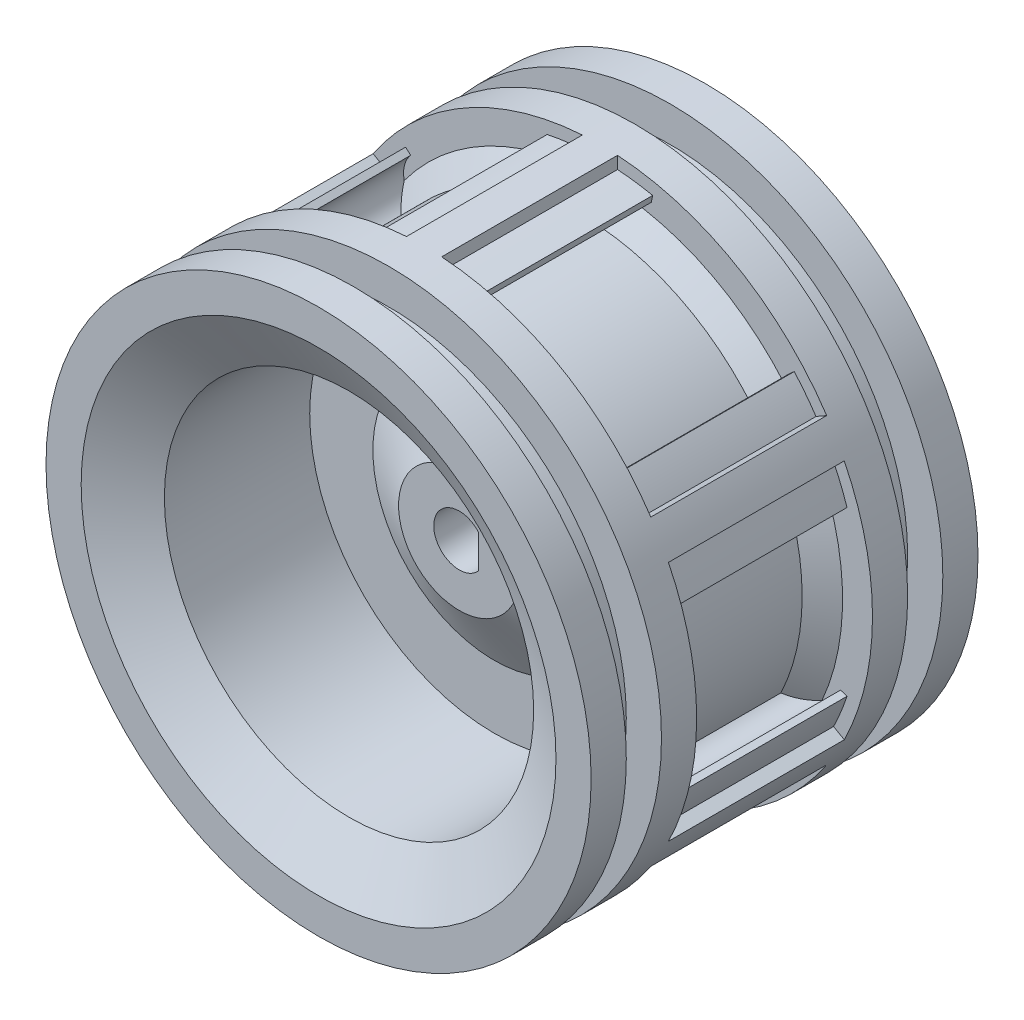
SolidWorks part; units mm, degrees
material "ABS"
ref_plane "Спереди" through (0, 0, 0) normal (0, 0, 1) x (1, 0, 0)
ref_plane "Сверху" through (0, 0, 0) normal (0, 1, 0) x (1, 0, 0)
ref_plane "Справа" through (0, 0, 0) normal (1, 0, 0) x (0, 0, -1)
sketch "Эскиз2" plane through (0, 0, 0) normal (1, 0, 0) x (0, 0, -1)
  line L0 (0, 19.2781) -> (0, -11.4066) construction
  line L1 (-12.1445, 0) -> (10.5473, 0) construction
  line L2 (4, 12.5) -> (-4, 12.5)
  line L3 (-4, 12.5) -> (-5, 13.799)
  line L4 (-5, 13.799) -> (-5, 15.5)
  line L5 (-5, 15.5) -> (-7, 15.5)
  line L6 (-7, 15.5) -> (-7, 13.5)
  line L7 (-7, 13.5) -> (-9, 13.5)
  line L8 (-9, 13.5) -> (-9, 15.5)
  line L9 (-9, 15.5) -> (-11, 15.5)
  line L10 (-11, 15.5) -> (-11, 13.5)
  line L11 (-11, 13.5) -> (-9.2679, 10.5)
  line L12 (-9.2679, 10.5) -> (-1.0033, 10.5)
  line L15 (10.5, 10.5) -> (10.5, 4.45)
  line L17 (11, 15.5) -> (11, 13.5)
  line L18 (9, 15.5) -> (11, 15.5)
  line L19 (9, 13.5) -> (9, 15.5)
  line L20 (7, 13.5) -> (9, 13.5)
  line L21 (7, 15.5) -> (7, 13.5)
  line L22 (5, 15.5) -> (7, 15.5)
  line L23 (5, 13.799) -> (5, 15.5)
  line L24 (4, 12.5) -> (5, 13.799)
  line L25 (10.5, 1.45) -> (-3, 1.45)
  line L26 (-3, 1.45) -> (-3, 3.45)
  line L27 (-3, 3.45) -> (-1.0033, 6.9084)
  line L28 (-1.0033, 6.9084) -> (-1.0033, 10.5)
  line L31 (11, 13.5) -> (10.5, 10.5)
  line L32 (10.5, 1.45) -> (13.5, 1.45)
  line L33 (10.5, 6.2924) -> (10.5, -2.5086) construction
  arc A0 (13.5, 1.45) -> (11.5, 3.45) centre (11.5, 1.45) ccw
  arc A1 (11.5, 3.45) -> (10.5, 4.45) centre (11.5, 4.45) cw
  dimension "D1" = 2
  dimension "D17" = 3
  dimension "D18" = 1
  dimension "D19" = 2
  dimension "D2" = 31
  dimension "D3" = 2
  dimension "D4" = 2
  dimension "D5" = 2
  dimension "D6" = 3
  dimension "D7" = 8
  dimension "D8" = 10
  dimension "D9" = 2
  dimension "D10" = 60
  dimension "D11" = 3
  dimension "D12" = 2.9
  dimension "D13" = 0.5
  dimension "D14" = 30
  dimension "D15" = 2
  dimension "D16" = 14
revolve "Повернуть1" add sketch "Эскиз2" angle 360 about L1 region at (0, 8.2036, -3.011)
sketch "Эскиз3" plane through (0, 0, 1.0033) normal (0, 0, 1) x (1, 0, 0)
  line L0 (-3.8268, 9.2388) -> (0, 0) construction
  line L1 (0, 0) -> (3.8268, 9.2388) construction
  line L2 (0, 16.141) -> (0, -17.0298) construction
  line L3 (-3.8268, 9.2388) -> (-2.8351, 6.8444) construction
  arc A1 (-3.8268, 9.2388) -> (3.8268, 9.2388) centre (0, 0) cw
  arc A2 (-2.8351, 6.8444) -> (2.8351, 6.8444) centre (0, 0) cw
  arc A3 (-2.8351, 6.8444) -> (-3.8268, 9.2388) centre (-3.3309, 8.0416) cw
  circle A4 centre (0, 0) radius 10.5 construction
  arc A5 (3.8268, 9.2388) -> (2.8351, 6.8444) centre (3.3309, 8.0416) cw
  circle A6 centre (0, 0) radius 6.9084 construction
  arc A7 (-3.3309, 8.0416) -> (3.3309, 8.0416) centre (0, 0) cw construction
  arc A8 (9.2388, -3.8268) -> (6.8444, -2.8351) centre (8.0416, -3.3309) cw
  arc A9 (6.8444, 2.8351) -> (6.8444, -2.8351) centre (0, 0) cw
  arc A10 (6.8444, 2.8351) -> (9.2388, 3.8268) centre (8.0416, 3.3309) cw
  arc A11 (9.2388, 3.8268) -> (9.2388, -3.8268) centre (0, 0) cw
  arc A12 (-3.8268, -9.2388) -> (-2.8351, -6.8444) centre (-3.3309, -8.0416) cw
  arc A13 (2.8351, -6.8444) -> (-2.8351, -6.8444) centre (0, 0) cw
  arc A14 (2.8351, -6.8444) -> (3.8268, -9.2388) centre (3.3309, -8.0416) cw
  arc A15 (3.8268, -9.2388) -> (-3.8268, -9.2388) centre (0, 0) cw
  arc A16 (-9.2388, 3.8268) -> (-6.8444, 2.8351) centre (-8.0416, 3.3309) cw
  arc A17 (-6.8444, -2.8351) -> (-6.8444, 2.8351) centre (0, 0) cw
  arc A18 (-6.8444, -2.8351) -> (-9.2388, -3.8268) centre (-8.0416, -3.3309) cw
  arc A19 (-9.2388, -3.8268) -> (-9.2388, 3.8268) centre (0, 0) cw
  point P51 (0, 0)
  dimension "D1" = 45
  dimension "D2" = 0.5
  dimension "D3" = 0.5
  dimension "D4" = 4
extrude "Вырез-Вытянуть1" [suppressed] cut sketch "Эскиз3" against normal through all contours A5 A1 A3 A2 | A11 A10 A9 A8 | A15 A14 A13 A12 | A19 A18 A17 A16
sketch "Эскиз4" plane through (0, 0, 0) normal (0, 0, 1) x (1, 0, 0)
  line L0 (-1, 15.4677) -> (-1, 14.7662)
  line L1 (1, 15.4677) -> (1, 14.7662)
  line L2 (0, 16.2065) -> (0, 0) construction
  line L7 (-3, 14.4928) -> (-2.9214, 14.1132)
  line L8 (3, 14.4928) -> (2.9214, 14.1132)
  line L9 (12.8954, 8.5999) -> (12.2879, 8.2491)
  line L10 (13.8954, 6.8678) -> (13.2879, 6.5171)
  line L11 (11.0511, 9.8445) -> (10.7617, 9.5866)
  line L12 (14.0511, 4.6483) -> (13.6831, 4.5266)
  line L13 (13.8954, -6.8678) -> (13.2879, -6.5171)
  line L14 (12.8954, -8.5999) -> (12.2879, -8.2491)
  line L15 (14.0511, -4.6483) -> (13.6831, -4.5266)
  line L16 (11.0511, -9.8445) -> (10.7617, -9.5866)
  line L17 (1, -15.4677) -> (1, -14.7662)
  line L18 (-1, -15.4677) -> (-1, -14.7662)
  line L19 (3, -14.4928) -> (2.9214, -14.1132)
  line L20 (-3, -14.4928) -> (-2.9214, -14.1132)
  line L21 (-12.8954, -8.5999) -> (-12.2879, -8.2491)
  line L22 (-13.8954, -6.8678) -> (-13.2879, -6.5171)
  line L23 (-11.0511, -9.8445) -> (-10.7617, -9.5866)
  line L24 (-14.0511, -4.6483) -> (-13.6831, -4.5266)
  line L25 (-13.8954, 6.8678) -> (-13.2879, 6.5171)
  line L26 (-12.8954, 8.5999) -> (-12.2879, 8.2491)
  line L27 (-14.0511, 4.6483) -> (-13.6831, 4.5266)
  line L28 (-11.0511, 9.8445) -> (-10.7617, 9.5866)
  arc A0 (-1, 15.4677) -> (1, 15.4677) centre (0, 0) cw
  arc A1 (-1, 12.4599) -> (1, 12.4599) centre (0, 0) cw
  circle A2 centre (0, 0) radius 12.5 construction
  arc A13 (-3, 14.4928) -> (-1, 14.7662) centre (0, 0) cw
  arc A16 (3, 14.4928) -> (1, 14.7662) centre (0, 0) ccw
  arc A17 (-2.9214, 14.1132) -> (-1, 12.4599) centre (-2.5972, 12.5468) cw
  arc A18 (2.9214, 14.1132) -> (1, 12.4599) centre (2.5972, 12.5468) ccw
  arc A19 (12.8954, 8.5999) -> (13.8954, 6.8678) centre (0, 0) cw
  arc A20 (10.2906, 7.096) -> (11.2906, 5.3639) centre (0, 0) cw
  arc A21 (11.0511, 9.8445) -> (12.2879, 8.2491) centre (0, 0) cw
  arc A22 (14.0511, 4.6483) -> (13.2879, 6.5171) centre (0, 0) ccw
  arc A23 (10.7617, 9.5866) -> (10.2906, 7.096) centre (9.5673, 8.5227) cw
  arc A24 (13.6831, 4.5266) -> (11.2906, 5.3639) centre (12.1645, 4.0242) ccw
  arc A25 (13.8954, -6.8678) -> (12.8954, -8.5999) centre (0, 0) cw
  arc A26 (11.2906, -5.3639) -> (10.2906, -7.096) centre (0, 0) cw
  arc A27 (14.0511, -4.6483) -> (13.2879, -6.5171) centre (0, 0) cw
  arc A28 (11.0511, -9.8445) -> (12.2879, -8.2491) centre (0, 0) ccw
  arc A29 (13.6831, -4.5266) -> (11.2906, -5.3639) centre (12.1645, -4.0242) cw
  arc A30 (10.7617, -9.5866) -> (10.2906, -7.096) centre (9.5673, -8.5227) ccw
  arc A31 (1, -15.4677) -> (-1, -15.4677) centre (0, 0) cw
  arc A32 (1, -12.4599) -> (-1, -12.4599) centre (0, 0) cw
  arc A33 (3, -14.4928) -> (1, -14.7662) centre (0, 0) cw
  arc A34 (-3, -14.4928) -> (-1, -14.7662) centre (0, 0) ccw
  arc A35 (2.9214, -14.1132) -> (1, -12.4599) centre (2.5972, -12.5468) cw
  arc A36 (-2.9214, -14.1132) -> (-1, -12.4599) centre (-2.5972, -12.5468) ccw
  arc A37 (-12.8954, -8.5999) -> (-13.8954, -6.8678) centre (0, 0) cw
  arc A38 (-10.2906, -7.096) -> (-11.2906, -5.3639) centre (0, 0) cw
  arc A39 (-11.0511, -9.8445) -> (-12.2879, -8.2491) centre (0, 0) cw
  arc A40 (-14.0511, -4.6483) -> (-13.2879, -6.5171) centre (0, 0) ccw
  arc A41 (-10.7617, -9.5866) -> (-10.2906, -7.096) centre (-9.5673, -8.5227) cw
  arc A42 (-13.6831, -4.5266) -> (-11.2906, -5.3639) centre (-12.1645, -4.0242) ccw
  arc A43 (-13.8954, 6.8678) -> (-12.8954, 8.5999) centre (0, 0) cw
  arc A44 (-11.2906, 5.3639) -> (-10.2906, 7.096) centre (0, 0) cw
  arc A45 (-14.0511, 4.6483) -> (-13.2879, 6.5171) centre (0, 0) cw
  arc A46 (-11.0511, 9.8445) -> (-12.2879, 8.2491) centre (0, 0) ccw
  arc A47 (-13.6831, 4.5266) -> (-11.2906, 5.3639) centre (-12.1645, 4.0242) cw
  arc A48 (-10.7617, 9.5866) -> (-10.2906, 7.096) centre (-9.5673, 8.5227) ccw
  point P80 (0, 0)
  dimension "D1" = 2
  dimension "D2" = 15.5
  dimension "D4" = 14.8
  dimension "D5" = 2
  dimension "D3" = 1.5996
extrude "Бобышка-Вытянуть1" add sketch "Эскиз4" along normal mid plane 10
sketch "Эскиз5" plane through (0, 0, 3) normal (0, 0, 1) x (1, 0, 0)
  line L0 (1.1, 0.9447) -> (1.1, -0.9447)
  line L1 (-1.8373, 0) -> (1.7808, 0) construction
  line L2 (0, 2.1043) -> (0, -2.0729) construction
  circle A0 centre (0, 0) radius 1.45 construction
  arc A1 (1.1, 0.9447) -> (1.1, -0.9447) centre (0, 0) cw
  circle A2 centre (0, 0) radius 1.5 construction
  point P9 (-1.45, 0)
  point P12 (-1.5, 0)
  dimension "D1" = 3
  dimension "D2" = 2.6
extrude "Бобышка-Вытянуть2" add sketch "Эскиз5" against normal through all
sketch "Эскиз6" plane through (0, 0, -10.5) normal (0, 0, -1) x (-1, 0, 0)
  line L0 (0, 15.0901) -> (0, -11.4305) construction
  line L1 (-4.6667, 8.8443) -> (-1.6667, 8.8443)
  line L2 (-6.8333, 5.8571) -> (-3.8333, 5.8571)
  line L3 (0, 7) -> (2.6441, 9.6441)
  line L4 (6.9694, 7.1713) -> (7.8964, 4.3181)
  line L5 (3.4588, 8.3088) -> (4.3859, 5.4557)
  line L6 (6.6574, 2.1631) -> (9.9892, 0.4655)
  line L7 (8.974, -4.4122) -> (6.5469, -6.1756)
  line L8 (8.971, -0.722) -> (6.5439, -2.4853)
  line L9 (4.1145, -5.6631) -> (3.5295, -9.3564)
  line L10 (-1.4232, -9.8982) -> (-3.8502, -8.1349)
  line L11 (2.0856, -8.755) -> (-0.3415, -6.9917)
  line L12 (-4.1145, -5.6631) -> (-7.8078, -6.2481)
  line L13 (-9.8535, -1.7052) -> (-8.9265, 1.148)
  line L14 (-7.682, -4.6889) -> (-6.755, -1.8358)
  line L15 (-6.6574, 2.1631) -> (-8.355, 5.4949)
  arc A0 (2.6441, 9.6441) -> (-4.6667, 8.8443) centre (0, 0) ccw
  arc A1 (-1.6667, 8.8443) -> (-6.8333, 5.8571) centre (0, 0) ccw
  arc A2 (-3.8333, 5.8571) -> (0, 7) centre (0, 0) cw
  arc A4 (9.9892, 0.4655) -> (6.9694, 7.1713) centre (0, 0) ccw
  arc A5 (7.8964, 4.3181) -> (3.4588, 8.3088) centre (0, 0) ccw
  arc A6 (4.3859, 5.4557) -> (6.6574, 2.1631) centre (0, 0) cw
  arc A7 (3.5295, -9.3564) -> (8.974, -4.4122) centre (0, 0) ccw
  arc A8 (6.5469, -6.1756) -> (8.971, -0.722) centre (0, 0) ccw
  arc A9 (6.5439, -2.4853) -> (4.1145, -5.6631) centre (0, 0) cw
  arc A10 (-7.8078, -6.2481) -> (-1.4232, -9.8982) centre (0, 0) ccw
  arc A11 (-3.8502, -8.1349) -> (2.0856, -8.755) centre (0, 0) ccw
  arc A12 (-0.3415, -6.9917) -> (-4.1145, -5.6631) centre (0, 0) cw
  arc A13 (-8.355, 5.4949) -> (-9.8535, -1.7052) centre (0, 0) ccw
  arc A14 (-8.9265, 1.148) -> (-7.682, -4.6889) centre (0, 0) ccw
  arc A15 (-6.755, -1.8358) -> (-6.6574, 2.1631) centre (0, 0) cw
  point P37 (0, 0)
  dimension "D1" = 45
  dimension "D2" = 10
  dimension "D4" = 9
  dimension "D6" = 7
  dimension "D3" = 3
  dimension "D5" = 3
extrude "Вырез-Вытянуть2" [suppressed] cut sketch "Эскиз6" against normal up to next
fillet "Скругление1" [suppressed] radius 0.2
